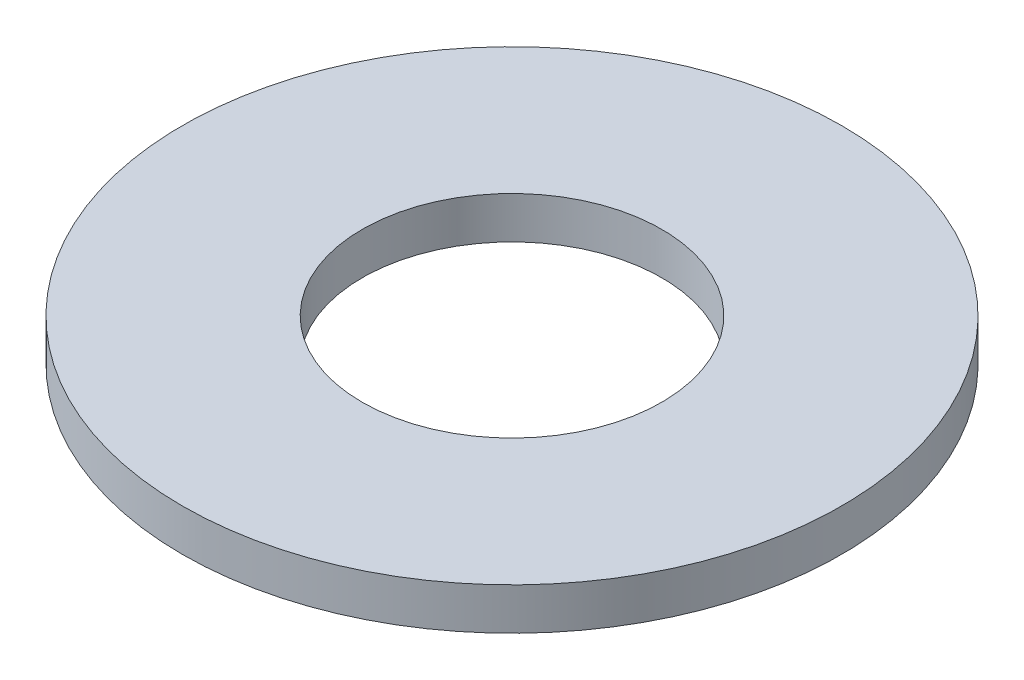
SolidWorks part; units mm, degrees
ref_plane "Front Plane" through (0, 0, 0) normal (0, 0, 1) x (1, 0, 0)
ref_plane "Top Plane" through (0, 0, 0) normal (0, 1, 0) x (1, 0, 0)
ref_plane "Right Plane" through (0, 0, 0) normal (1, 0, 0) x (0, 0, -1)
sketch "Sketch1" plane through (0, 0, 0) normal (0, 1, 0) x (1, 0, 0)
  circle A0 centre (0, 0) radius 55
  dimension "FLANGE_OD" = 110
extrude "Boss-Extrude1" add sketch "Sketch1" along normal blind 7
sketch "Sketch2" plane through (0, 0, 0) normal (0, 1, 0) x (1, 0, 0)
  circle A0 centre (0, 0) radius 25
  dimension "BORE_D" = 50
extrude "Cut-Extrude1" cut sketch "Sketch2" along normal through all
sketch "Sketch3" plane through (0, 7, 0) normal (0, 1, 0) x (1, 0, 0)
  circle A0 centre (0, 0) radius 16.5625 construction
  circle A1 centre (-16.5625, 0) radius 3.8557
  dimension "BOLT_D" = 7.7113
  dimension "BOLT_PCD" = 33.125
extrude "Cut-Extrude2" cut sketch "Sketch3" against normal blind 4.7768 rebuild error yes
pattern_circular "CirPattern1" count 5 over 360 rebuild error yes
